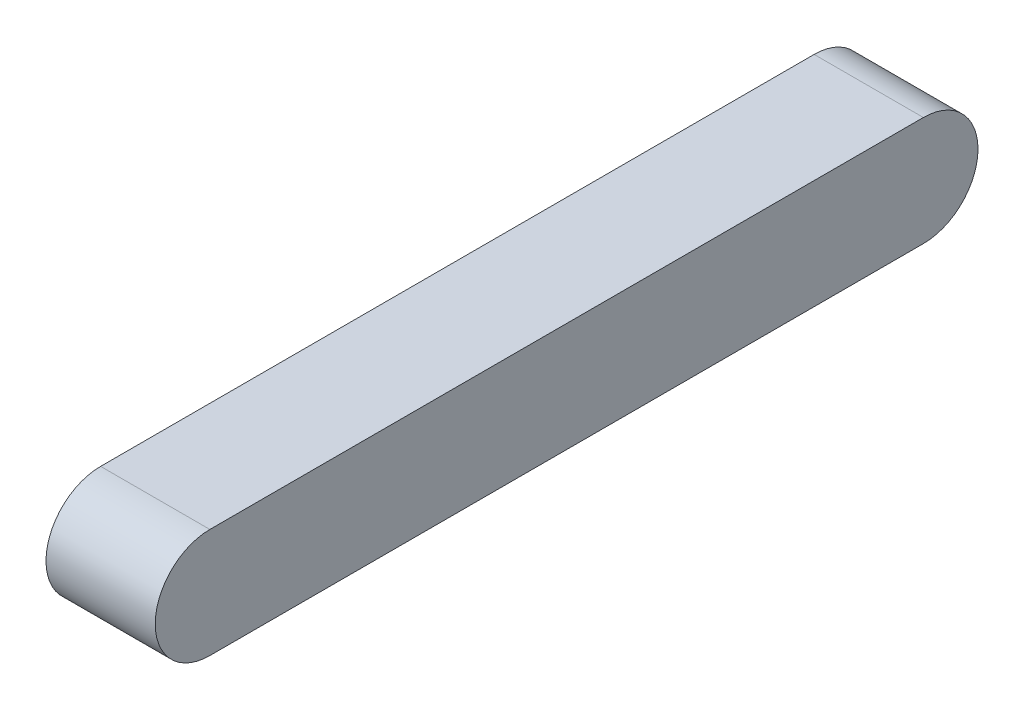
SolidWorks part; units mm, degrees
ref_plane "Płaszczyzna przednia" through (0, 0, 0) normal (0, 0, 1) x (1, 0, 0)
ref_plane "Płaszczyzna górna" through (0, 0, 0) normal (0, 1, 0) x (1, 0, 0)
ref_plane "Płaszczyzna prawa" through (0, 0, 0) normal (1, 0, 0) x (0, 0, -1)
sketch "Szkic1" plane through (0, 0, 0) normal (0, 0, 1) x (1, 0, 0)
  line L1 (-2.39, 2.39) -> (2.39, 2.39)
  line L2 (-2.39, 2.39) -> (-2.39, -2.39)
  line L3 (-2.39, -2.39) -> (2.39, -2.39)
  line L4 (2.39, 2.39) -> (2.39, -2.39)
  point P4 (0, -2.39)
  point P5 (-2.39, 0)
  dimension "D1" = 4.78
  dimension "D2" = 4.78
extrude "Dodanie-wyciągnięcie1" add sketch "Szkic1" along normal blind 36 contours L3 L4 L1 L2
fillet "Zaokrąglenie1" 2 edges at (0, 2.39, 36) (0, -2.39, 36) type full round first side face at (0, 2.39, 18) second side face at (0, -2.39, 18) middle face at (0, 0, 36)
fillet "Zaokrąglenie2" 2 edges at (0, 2.39, 0) (0, -2.39, 0) type full round first side face at (0, 2.39, 16.805) second side face at (0, -2.39, 16.805) middle face at (0, 0, 0)
